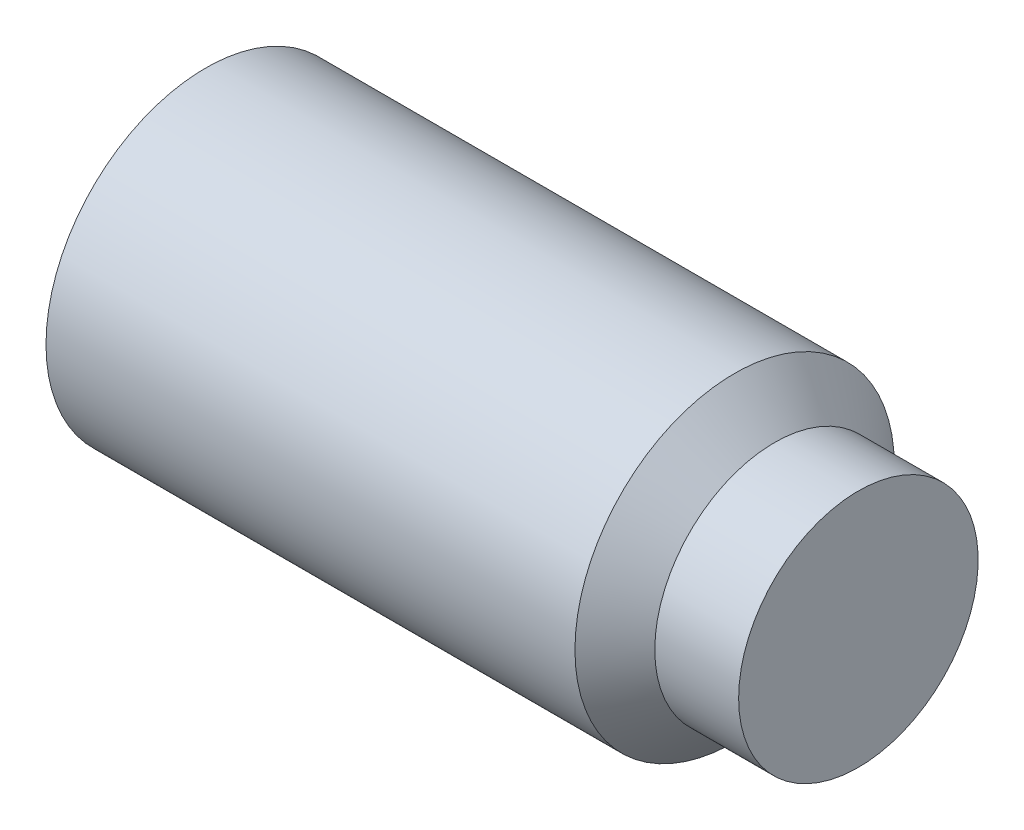
SolidWorks part; units mm, degrees
revolve "BaseBody" add sketch "BodySke" angle 360 about L5 other way angle 60
sketch "BodySke" plane through (0, 0, 0) normal (0, 0, 1) x (1, 0, 0)
  line L0 (0, 0) -> (0, 10.352)
  line L1 (0, 10.352) -> (0.9515, 12)
  line L2 (0.9515, 12) -> (40.7, 12)
  line L3 (40.7, 12) -> (43.7, 9)
  line L4 (50, 0) -> (0, 0)
  line L5 (-12.7, 0) -> (88.9, 0) construction
  line L6 (43.7, 9) -> (50, 9)
  line L7 (50, 9) -> (50, 0)
  line L8 (0, -10.352) -> (0.9515, -12) construction
  line L9 (43.7, -9) -> (50, -9) construction
  line L10 (1.5, 15.875) -> (1.5, -3.175) construction
  dimension "Length" = 50
  dimension "D1" = 45
  dimension "Advance" = 3
  dimension "Diameter" = 24
cosmetic thread "ThreadCosmetic" [suppressed] parameters "Thread_minor"=20.704
ref_plane "Plane1" through (0, 0, 0) normal (0, 0, 1) x (1, 0, 0)
ref_plane "Plane2" through (0, 0, 0) normal (0, 1, 0) x (1, 0, 0)
ref_plane "Plane3" through (0, 0, 0) normal (1, 0, 0) x (0, 0, -1)
sketch "Sketch2" plane through (0, 0, 0) normal (-1, 0, 0) x (0, 0, 1)
  line L0 (3.4641, 6) -> (-3.4641, 6)
  line L1 (-3.4641, 6) -> (-6.9282, 0)
  line L2 (3.4641, 6) -> (6.9282, 0)
  line L3 (3.4641, -6) -> (6.9282, 0)
  line L4 (3.4641, -6) -> (-3.4641, -6)
  line L5 (-3.4641, -6) -> (-6.9282, 0)
  dimension "D2" = 6
  dimension "D3" = 6
extrude "Hex" cut sketch "Sketch2" against normal blind 15
sketch "ThdSchSke" plane through (0, 0, 0) normal (0, 0, 1) x (1, 0, 0)
  line L0 (0.9515, -10.352) -> (-0.2025, -12)
  line L1 (0.9515, -10.352) -> (2.1054, -12)
  line L2 (2.1054, -12) -> (2.1054, -15)
  line L3 (-3.175, 0) -> (5.1513, 0) construction
  line L4 (0.9515, 12) -> (0.9515, -12) construction
  line L5 (2.1054, -15) -> (-0.2025, -15)
  line L6 (-0.2025, -15) -> (-0.2025, -12)
  dimension "Thread_minor" = 20.704
  dimension "Diameter" = 24
revolve "ThreadSchematic" [suppressed] cut sketch "ThdSchSke" angle 360 about L3
pattern_linear "ThdSchPat" [suppressed]
equation "\"D2@Sketch2\" = \"Hex_size@Sketch2\" / 2"
equation "\"D3@Sketch2\" = \"Hex_size@Sketch2\" / 2"
equation "\"Thread_minor@ThreadCosmetic\" = \"Minor_dia@BodySke\""
equation "\"Thread_minor@ThdSchSke\" = \"Thread_minor@ThreadCosmetic\""
equation "\"Diameter@ThdSchSke\" = \"Diameter@BodySke\""
equation "\"Overcut@ThdSchSke\" = \"Diameter@BodySke\" * 1.25"
equation "\"Num_threads@ThdSchPat\" = int( (\"Length@BodySke\" - ( ( ( \"Diameter@BodySke\" - \"Minor_dia@BodySke\" ) * 0.5 ) / tan( \"Drive_ch_ang@BodySke\" * 0.017453292 ) ) - \"Dog_len@BodySke\" ) / \"Advance@BodySke\" + 0.999 )  + 1"
equation "\"Advance@ThdSchPat\" = (\"Length@BodySke\" - ( ( ( \"Diameter@BodySke\" - \"Minor_dia@BodySke\" ) * 0.5 ) / tan( \"Drive_ch_ang@BodySke\" * 0.017453292 ) ) - \"Dog_len@BodySke\" ) /  (\"Num_threads@ThdSchPat\" - 1) 'relax it"
equation "\"Num_threads@ThdSchPat\" = \"Num_threads@ThdSchPat\" - sgn( \"Num_threads@ThdSchPat\" - 1) '---chamfered tips only---"
